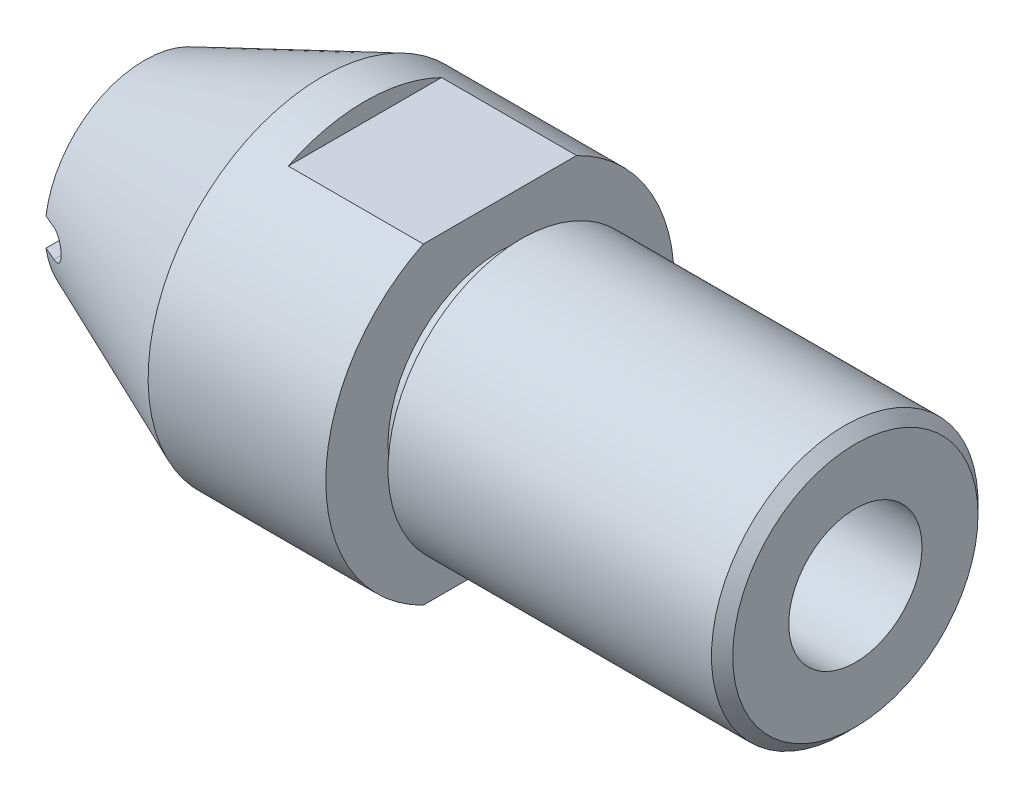
SolidWorks part; units mm, degrees
material "S-7 Tool Steel"
ref_plane "Front Plane" through (0, 0, 0) normal (0, 0, 1) x (1, 0, 0)
ref_plane "Top Plane" through (0, 0, 0) normal (0, 1, 0) x (1, 0, 0)
ref_plane "Right Plane" through (0, 0, 0) normal (1, 0, 0) x (0, 0, -1)
sketch "Sketch1" plane through (0, 0, 0) normal (0, 0, 1) x (1, 0, 0)
  line L0 (0, 0) -> (0, 7.112)
  line L1 (0, 7.112) -> (12.7, 12.446)
  line L2 (12.7, 12.446) -> (25.4, 12.446)
  line L3 (25.4, 12.446) -> (25.4, 8.001)
  line L4 (25.4, 8.001) -> (26.924, 8.001)
  line L5 (26.924, 8.001) -> (26.924, 9.525)
  line L6 (26.924, 9.525) -> (50.8, 9.525)
  line L7 (50.8, 9.525) -> (50.8, 0)
  line L8 (50.8, 0) -> (0, 0)
  dimension "D1" = 7.112
  dimension "D2" = 12.446
  dimension "D3" = 1.524
  dimension "D4" = 12.7
  dimension "D5" = 12.7
  dimension "D6" = 25.4
  dimension "D7" = 9.525
  dimension "D8" = 1.524
revolve "Revolve1" add sketch "Sketch1" angle 360 about L8
cosmetic thread "Cosmetic Thread1" parameters "D2"=17.4752
chamfer "Chamfer1" distance 0.762 angle 45 1 edges at (50.8, 9.525, 0)
hole_wizard "3/8 (0.375) Diameter Hole1" positions "Sketch3" profile "Sketch2" hole size "3/8" standard "Ansi Inch"
sketch "Sketch3" plane through (50.8, 0, 0) normal (1, 0, 0) x (0, 0, -1)
  point P0 (0, 0)
sketch "Sketch2" plane through (50.8, 0, 0) normal (0, 1, 0) x (0, 0, -1)
  line L0 (0, 0) -> (0, 39.8334)
  line L1 (0, 39.8334) -> (4.7625, 38.1)
  line L2 (4.7625, 38.1) -> (4.7625, 0)
  line L5 (4.7625, 0) -> (0, 0)
  line L10 (0, 39.8334) -> (-4.7625, 38.1) construction
  line L11 (0, -6.35) -> (0, 107.95) construction
  dimension "Hole Dia." = 9.525
  dimension "Hole Depth" = 38.1
  dimension "Drill Angle" = 140
hole_wizard "3/8 (0.375) Diameter Hole2" positions "Sketch5" profile "Sketch4" hole size "3/8" standard "Ansi Inch"
sketch "Sketch5" plane through (0, 0, 0) normal (-1, 0, 0) x (0, 0, 1)
  point P0 (0, 0)
sketch "Sketch4" plane through (0, 0, 0) normal (0, 1, 0) x (0, 0, 1)
  line L0 (0, 0) -> (0, 38.3773)
  line L1 (0, 38.3773) -> (0.762, 38.1)
  line L2 (0.762, 38.1) -> (0.762, 0)
  line L5 (0.762, 0) -> (0, 0)
  line L10 (0, 38.3773) -> (-0.762, 38.1) construction
  line L11 (0, -6.35) -> (0, 107.95) construction
  dimension "Hole Dia." = 1.524
  dimension "Hole Depth" = 38.1
  dimension "Drill Angle" = 140
hole_wizard "3/8 (0.375) Diameter Hole3" positions "Sketch9" profile "Sketch8" hole size "3/8" standard "Ansi Inch"
sketch "Sketch9" plane through (0, 0, 0) normal (-1, 0, 0) x (0, 0, 1)
  point P0 (0, 0)
sketch "Sketch8" plane through (0, 0, 0) normal (0, 1, 0) x (0, 0, 1)
  line L0 (0, 0) -> (0, 6.5825)
  line L1 (0, 6.5825) -> (4.826, 4.826)
  line L2 (4.826, 4.826) -> (4.826, 0)
  line L5 (4.826, 0) -> (0, 0)
  line L10 (0, 6.5825) -> (-4.826, 4.826) construction
  line L11 (0, -6.35) -> (0, 107.95) construction
  dimension "Hole Dia." = 9.652
  dimension "Hole Depth" = 4.826
  dimension "Drill Angle" = 140
sketch "Sketch10" plane through (0, 0, 0) normal (0, 0, 1) x (1, 0, 0)
  line L0 (25.4, -12.446) -> (25.4, 12.446) construction
  line L1 (15.748, 13.8039) -> (25.4, 13.8039)
  line L2 (15.748, 13.8039) -> (15.748, 11.176)
  line L3 (15.748, 11.176) -> (25.4, 11.176)
  line L4 (25.4, 13.8039) -> (25.4, 11.176)
  line L6 (25.4, -11.176) -> (15.748, -11.176)
  line L7 (25.4, -11.176) -> (25.4, -17.526)
  line L8 (25.4, -17.526) -> (15.748, -17.526)
  line L9 (15.748, -11.176) -> (15.748, -17.526)
  dimension "D1" = 11.176
  dimension "D2" = 11.176
  dimension "D3" = 6.35
  dimension "D4" = 2.6279
  dimension "D5" = 9.652
  dimension "D6" = 9.652
extrude "Extrude1" cut sketch "Sketch10" against normal blind 25.4 and the other way blind 25.4
sketch "Sketch11" plane through (0, 0, 0) normal (0, 0, 1) x (1, 0, 0)
  line L0 (0, 0.9922) -> (0, -0.9922)
  line L1 (0, 0) -> (0.0584, 0) construction
  line L2 (0, 0) -> (0.9922, 0) construction
  line L5 (0, 0.9922) -> (0.9922, 0.9922)
  line L6 (0, -0.9922) -> (0.9922, -0.9922)
  arc A3 (0.9922, -0.9922) -> (0.9922, 0.9922) centre (0.9922, 0) ccw
  dimension "D2" = 0.9922
  dimension "D1" = 1.9844
extrude "Cut-Extrude1" cut sketch "Sketch11" against normal mid plane 25.4
